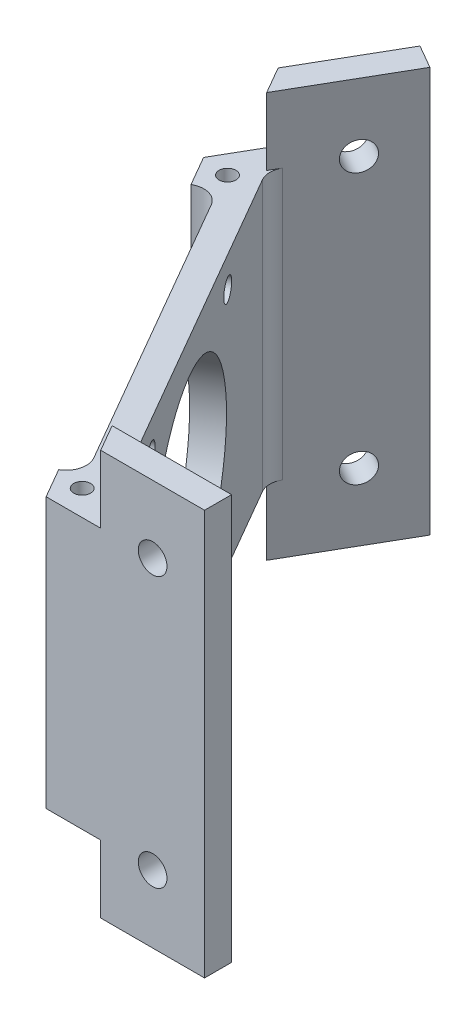
SolidWorks part; units mm, degrees
ref_plane "Front Plane" through (0, 0, 0) normal (0, 0, 1) x (1, 0, 0)
ref_plane "Top Plane" through (0, 0, 0) normal (0, 1, 0) x (1, 0, 0)
ref_plane "Right Plane" through (0, 0, 0) normal (1, 0, 0) x (0, 0, -1)
sketch "Sketch1" plane through (0, 0, 0) normal (0, 1, 0) x (1, 0, 0)
  line L9 (0, 0) -> (48, 0) construction
  line L10 (48, 0) -> (404, 0) construction
  line L11 (404, 0) -> (452, 0) construction
  line L12 (452, 0) -> (428, 41.5692) construction
  line L13 (428, 41.5692) -> (250, 349.8743) construction
  line L14 (250, 349.8743) -> (226, 391.4435) construction
  line L15 (226, 391.4435) -> (202, 349.8743) construction
  line L16 (202, 349.8743) -> (24, 41.5692) construction
  line L17 (24, 41.5692) -> (0, 0) construction
  line L18 (48, 0) -> (24, 41.5692) construction
  line L19 (202, 349.8743) -> (250, 349.8743) construction
  line L20 (428, 41.5692) -> (404, 0) construction
  line L22 (15.3397, 46.5692) -> (193.3397, 354.8743) construction
  line L28 (404, -10) -> (48, -10) construction
  line L30 (48, -10) -> (48, 10) construction
  line L31 (404, -10) -> (404, 10) construction
  line L32 (15.3397, 46.5692) -> (32.6603, 36.5692) construction
  line L33 (193.3397, 354.8743) -> (210.6603, 344.8743) construction
  line L34 (404, 10) -> (48, 10) construction
  line L35 (32.6603, 36.5692) -> (210.6603, 344.8743) construction
  line L36 (48, -10) -> (48, 10) construction
  line L37 (48, 10) -> (84.5, 10) construction
  line L38 (15.3397, 46.5692) -> (32.6603, 36.5692) construction
  line L39 (32.6603, 36.5692) -> (50.9103, 68.1791) construction
  line L40 (50.9103, 68.1791) -> (53.2197, 64.1791) construction
  line L41 (53.2197, 64.1791) -> (37.1147, 36.2846) construction
  line L42 (37.1147, 33.2846) -> (47.3827, 15.5) construction
  line L43 (49.9808, 14) -> (82.1906, 14) construction
  line L44 (82.1906, 14) -> (84.5, 10) construction
  line L45 (0, 0) -> (42.2487, 24.3923) construction
  line L52 (84.5, 10) -> (104.5, 10)
  line L53 (104.5, 10) -> (104.5, 14)
  line L54 (104.5, 14) -> (88.5415, 14)
  line L55 (85.9434, 15.5) -> (56.3951, 66.6791)
  line L56 (56.3951, 69.6791) -> (64.3744, 83.4997)
  line L57 (64.3744, 83.4997) -> (60.9103, 85.4997)
  line L58 (60.9103, 85.4997) -> (50.9103, 68.1791)
  line L59 (50.9103, 68.1791) -> (46.8688, 61.1791)
  line L60 (46.8688, 61.1791) -> (49.1782, 57.1791)
  line L61 (49.1782, 57.1791) -> (53.2197, 64.1791)
  line L62 (53.2197, 64.1791) -> (82.1906, 14)
  line L63 (82.1906, 14) -> (74.1077, 14)
  line L64 (74.1077, 14) -> (76.4171, 10)
  line L65 (76.4171, 10) -> (84.5, 10)
  arc A0 (48, -10) -> (15.3397, 46.5692) centre (48, 27.7128) cw construction
  arc A1 (49.9808, 14) -> (47.3827, 15.5) centre (49.9808, 17) cw construction
  arc A2 (37.1147, 33.2846) -> (37.1147, 36.2846) centre (39.7128, 34.7846) cw construction
  arc A3 (56.3951, 69.6791) -> (56.3951, 66.6791) centre (58.9932, 68.1791) ccw
  arc A4 (85.9434, 15.5) -> (88.5415, 14) centre (88.5415, 17) ccw
  point P27 (48.2487, 14)
  point P30 (36.2487, 34.7846)
  dimension "D7" = 3
  dimension "D10" = 3
  dimension "D1" = 356
  dimension "D2" = 48
  dimension "D3" = 10
  dimension "D4" = 36.5
  dimension "D5" = 4
  dimension "D6" = 24
  dimension "D8" = 4
  dimension "D9" = 4
  dimension "D11" = 20
  dimension "D12" = 8.0829
extrude "Boss-Extrude4" add sketch "Sketch1" along normal blind 60
sketch "Sketch12" plane through (0, 60, 0) normal (0, 1, 0) x (1, 0, 0)
  line L2 (76.4171, 10) -> (104.5, 10) construction
  line L3 (89.1188, 10) -> (76.4171, 10)
  line L4 (76.4171, 10) -> (46.8688, 61.1791)
  line L5 (46.8688, 61.1791) -> (53.2197, 72.1791)
  line L6 (60.9103, 85.4997) -> (46.8688, 61.1791) construction
  line L8 (56.3951, 66.6791) -> (85.9434, 15.5)
  line L9 (56.3951, 69.6791) -> (55.5291, 68.1791)
  line L10 (55.5291, 68.1791) -> (53.2197, 72.1791)
  line L11 (60.9103, 85.4997) -> (50.9103, 68.1791) construction
  line L13 (88.5415, 14) -> (86.8094, 14)
  line L14 (86.8094, 14) -> (89.1188, 10)
  line L15 (84.5, 10) -> (104.5, 10) construction
  arc A0 (85.9434, 15.5) -> (88.5415, 14) centre (88.5415, 17) ccw
  arc A1 (56.3951, 66.6791) -> (56.3951, 69.6791) centre (58.9932, 68.1791) cw
extrude "Cut-Extrude9" cut sketch "Sketch12" against normal blind 10
ref_plane "Plane3" through (0, 30, 0) normal (0, 1, 0) x (1, 0, 0)
mirror "Mirror4" about plane through (0, 30, 0) normal (0, 1, 0) of "Cut-Extrude9"
fillet "Fillet5" radius 3 2 edges at (53.2197, 30, -64.1791) (82.1906, 30, -14)
sketch "Sketch13" plane through (0, 50, 0) normal (0, 1, 0) x (1, 0, 0)
  circle A0 centre (53.2197, 64.6791) radius 1.25
  circle A1 centre (82.6236, 13.75) radius 1.25
  dimension "D5" = 2.5
  dimension "D1" = 53.2197
  dimension "D2" = 64.6791
  dimension "D3" = 82.6236
  dimension "D4" = 13.75
extrude "Cut-Extrude10" cut sketch "Sketch13" against normal through all
sketch "Sketch14" plane through (0, 0, -10) normal (0, 0, 1) x (1, 0, 0)
  line L0 (104.5, 50) -> (89.1188, 50) construction
  line L1 (104.5, 60) -> (104.5, 0) construction
  line L2 (89.1188, 50) -> (89.1188, 60) construction
  line L3 (104.5, 10) -> (89.1188, 10) construction
  line L4 (89.1188, 10) -> (89.1188, 0) construction
  line L5 (89.1188, 60) -> (104.5, 60) construction
  line L6 (89.1188, 0) -> (104.5, 0) construction
  circle A0 centre (96.8094, 50) radius 2.125
  circle A1 centre (96.8094, 10) radius 2.125
  dimension "D3" = 4.25
  dimension "D1" = 10
  dimension "D2" = 10
extrude "Cut-Extrude11" cut sketch "Sketch14" against normal up to surface (4 mm away) up to face at (91.6651, 30, -14)
sketch "Sketch15" plane through (8.6603, 0, 5) normal (-0.866, 0, -0.5) x (-0.5, 0, 0.866)
  line L0 (-104.5, 50) -> (-89.1188, 50) construction
  line L1 (-104.5, 60) -> (-104.5, 0) construction
  line L2 (-89.1188, 50) -> (-89.1188, 60) construction
  line L3 (-104.5, 10) -> (-89.1188, 10) construction
  line L4 (-89.1188, 10) -> (-89.1188, 0) construction
  line L5 (-104.5, 60) -> (-89.1188, 60) construction
  line L6 (-104.5, 0) -> (-89.1188, 0) construction
  circle A0 centre (-96.8094, 50) radius 2.125
  circle A1 centre (-96.8094, 10) radius 2.125
  dimension "D3" = 4.25
  dimension "D1" = 10
  dimension "D2" = 10
extrude "Cut-Extrude12" cut sketch "Sketch15" against normal up to surface (4 mm away) up to face at (57.9569, 30, -72.3843)
sketch "Sketch16" plane through (71.1692, 0, -41.0896) normal (0.866, 0, -0.5) x (-0.5, 0, -0.866)
  line L0 (0, 50) -> (0, 10) construction
  line L1 (-29.5483, 50) -> (29.5483, 50) construction
  line L2 (-29.5483, 10) -> (29.5483, 10) construction
  circle A0 centre (0, 30) radius 15
  circle A1 centre (-15.5, 45.5) radius 1.6
  circle A2 centre (15.5, 45.5) radius 1.6
  circle A3 centre (15.5, 14.5) radius 1.6
  circle A4 centre (-15.5, 14.5) radius 1.6
  dimension "D1" = 30
  dimension "D2" = 3.2
  dimension "D3" = 15.5
  dimension "D4" = 15.5
  dimension "D5" = 31
  dimension "D6" = 31
extrude "Cut-Extrude13" cut sketch "Sketch16" against normal up to surface (4 mm away) up to face at (67.7051, 30, -39.0896)
sketch "Sketch17" plane through (0, 50, 0) normal (0, 1, 0) x (1, 0, 0)
  line L0 (46.8688, 61.1791) -> (76.4171, 10)
  line L1 (76.4171, 10) -> (81.0358, 10)
  line L2 (76.4171, 10) -> (89.1188, 10) construction
  line L3 (81.0358, 10) -> (49.1782, 65.1791)
  line L4 (53.2197, 72.1791) -> (46.8688, 61.1791) construction
  line L5 (49.1782, 65.1791) -> (46.8688, 61.1791)
  dimension "D1" = 4.6187
extrude "Cut-Extrude14" cut sketch "Sketch17" against normal up to surface (40 mm away) up to face at (53.2197, 10, -63.4291)
